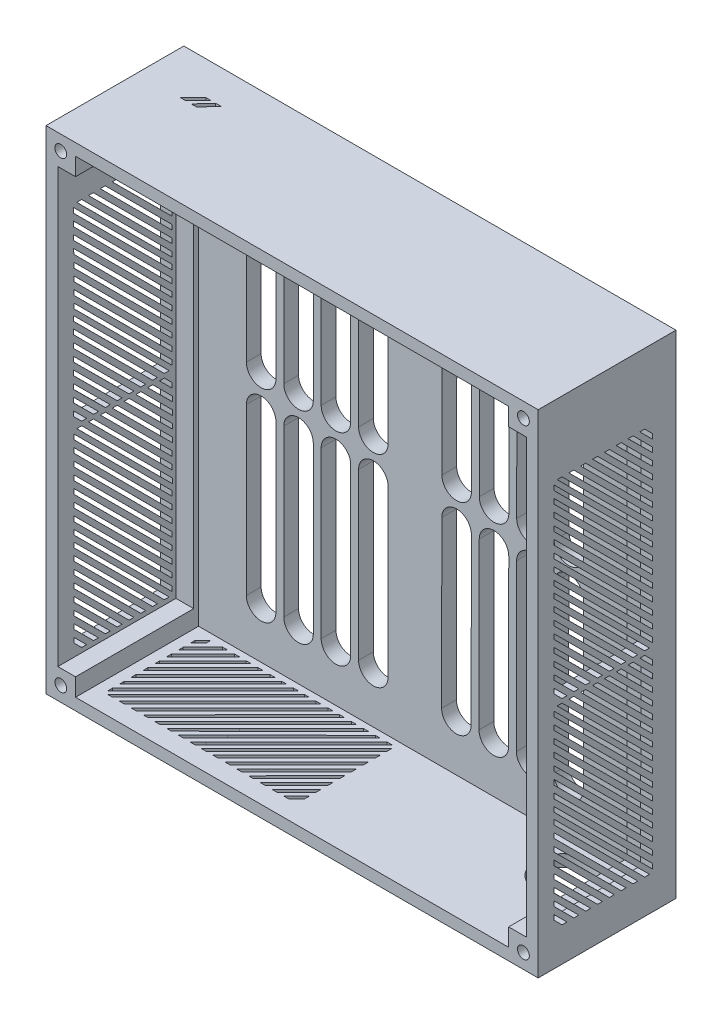
SolidWorks part; units mm, degrees
ref_plane "Plano frontal" through (0, 0, 0) normal (0, 0, 1) x (1, 0, 0)
ref_plane "Plano superior" through (0, 0, 0) normal (0, 1, 0) x (1, 0, 0)
ref_plane "Plano direito" through (0, 0, 0) normal (1, 0, 0) x (0, 0, -1)
sketch "Esboço1" plane through (0, 0, 0) normal (0, 0, 1) x (1, 0, 0)
  line L1 (-16.5696, 239.8339) -> (233.4304, 239.8339)
  line L2 (-16.5696, 239.8339) -> (-16.5696, -10.1661)
  line L3 (-16.5696, -10.1661) -> (233.4304, -10.1661)
  line L4 (233.4304, 239.8339) -> (233.4304, -10.1661)
  dimension "D1" = 250
  dimension "D2" = 250
extrude "Ressalto-extrusão1" add sketch "Esboço1" along normal blind 70 contours L2 L1 L4 L3
sketch "Esboço2" plane through (0, 0, 70) normal (0, 0, 1) x (1, 0, 0)
  line L0 (233.4304, 239.8339) -> (233.4304, -10.1661) construction
  line L1 (-10.5696, 233.8339) -> (227.4304, 233.8339)
  line L2 (-10.5696, 233.8339) -> (-10.5696, -4.1661)
  line L3 (-10.5696, -4.1661) -> (227.4304, -4.1661)
  line L4 (227.4304, 233.8339) -> (227.4304, -4.1661)
  line L5 (-16.5696, 239.8339) -> (233.4304, 239.8339) construction
  line L6 (-16.5696, 239.8339) -> (-16.5696, -10.1661) construction
  line L7 (-16.5696, -10.1661) -> (233.4304, -10.1661) construction
  dimension "D1" = 6
  dimension "D2" = 6
  dimension "D3" = 6
  dimension "D4" = 6
extrude "Corte-extrusão1" cut sketch "Esboço2" against normal blind 60
sketch "Esboço3" plane through (0, 0, 10) normal (0, 0, 1) x (1, 0, 0)
  line L0 (16.5131, 123.2364) -> (114.7807, 123.244)
  line L1 (16.3207, 123.1057) -> (16.3131, 223.614)
  line L2 (16.3748, 223.7141) -> (114.8731, 223.7141)
  line L3 (114.7807, 123.244) -> (114.7731, 223.5216)
  line L4 (215.3156, 223.7537) -> (117.0479, 223.7536)
  line L5 (215.5079, 223.8844) -> (215.5079, 123.3761)
  line L6 (117.0479, 123.4759) -> (215.5079, 123.3761)
  line L7 (117.0479, 223.7536) -> (117.0479, 123.4759)
  line L10 (16.567, 20.9373) -> (114.8346, 20.9449)
  line L11 (16.3746, 20.8067) -> (16.367, 121.3149)
  line L12 (16.4288, 121.4073) -> (99.2081, 121.4137)
  line L13 (114.8346, 20.9449) -> (114.827, 121.2225)
  line L14 (215.3478, 121.4314) -> (117.0801, 121.4238)
  line L15 (215.5401, 121.5621) -> (215.5477, 21.0538)
  line L16 (215.486, 20.9614) -> (116.9877, 20.9538)
  line L17 (117.0801, 121.4238) -> (117.0877, 21.1462)
  line L21 (-16.5696, -10.1661) -> (233.4304, -10.1661) construction
  line L23 (114.7807, 123.244) -> (117.0801, 121.4238) construction
  line L24 (99.2081, 121.4137) -> (114.827, 121.2225)
  line L25 (-16.5696, 239.8339) -> (233.4304, -10.1661) construction
  line L26 (-16.5696, -10.1661) -> (233.4304, 239.8339) construction
  arc A0 (59.4431, 138.154) -> (59.4431, 125.154) centre (59.4431, 131.654) ccw
  arc A1 (59.4431, 125.154) -> (59.4431, 138.154) centre (59.4431, 131.654) ccw
  arc A2 (40.4431, 138.154) -> (40.4431, 125.154) centre (40.4431, 131.654) ccw
  arc A3 (40.4431, 125.154) -> (40.4431, 138.154) centre (40.4431, 131.654) ccw
  arc A4 (40.4431, 152.154) -> (40.4431, 139.154) centre (40.4431, 145.654) ccw
  arc A5 (40.4431, 139.154) -> (40.4431, 152.154) centre (40.4431, 145.654) ccw
  arc A6 (59.4431, 152.154) -> (59.4431, 139.154) centre (59.4431, 145.654) ccw
  arc A7 (59.4431, 139.154) -> (59.4431, 152.154) centre (59.4431, 145.654) ccw
  arc A8 (78.4431, 152.154) -> (78.4431, 139.154) centre (78.4431, 145.654) ccw
  arc A9 (78.4431, 139.154) -> (78.4431, 152.154) centre (78.4431, 145.654) ccw
  arc A10 (78.4431, 138.154) -> (78.4431, 125.154) centre (78.4431, 131.654) ccw
  arc A11 (78.4431, 125.154) -> (78.4431, 138.154) centre (78.4431, 131.654) ccw
  arc A12 (97.4431, 138.154) -> (97.4431, 125.154) centre (97.4431, 131.654) ccw
  arc A13 (97.4431, 125.154) -> (97.4431, 138.154) centre (97.4431, 131.654) ccw
  arc A14 (97.4431, 152.154) -> (97.4431, 139.154) centre (97.4431, 145.654) ccw
  arc A15 (97.4431, 139.154) -> (97.4431, 152.154) centre (97.4431, 145.654) ccw
  arc A16 (97.4431, 166.154) -> (97.4431, 153.154) centre (97.4431, 159.654) ccw
  arc A17 (97.4431, 153.154) -> (97.4431, 166.154) centre (97.4431, 159.654) ccw
  arc A18 (78.4431, 166.154) -> (78.4431, 153.154) centre (78.4431, 159.654) ccw
  arc A19 (78.4431, 153.154) -> (78.4431, 166.154) centre (78.4431, 159.654) ccw
  arc A20 (59.4431, 166.154) -> (59.4431, 153.154) centre (59.4431, 159.654) ccw
  arc A21 (59.4431, 153.154) -> (59.4431, 166.154) centre (59.4431, 159.654) ccw
  arc A22 (40.4431, 166.154) -> (40.4431, 153.154) centre (40.4431, 159.654) ccw
  arc A23 (40.4431, 153.154) -> (40.4431, 166.154) centre (40.4431, 159.654) ccw
  arc A24 (40.4431, 180.154) -> (40.4431, 167.154) centre (40.4431, 173.654) ccw
  arc A25 (40.4431, 167.154) -> (40.4431, 180.154) centre (40.4431, 173.654) ccw
  arc A26 (59.4431, 180.154) -> (59.4431, 167.154) centre (59.4431, 173.654) ccw
  arc A27 (59.4431, 167.154) -> (59.4431, 180.154) centre (59.4431, 173.654) ccw
  arc A28 (78.4431, 180.154) -> (78.4431, 167.154) centre (78.4431, 173.654) ccw
  arc A29 (78.4431, 167.154) -> (78.4431, 180.154) centre (78.4431, 173.654) ccw
  arc A30 (97.4431, 180.154) -> (97.4431, 167.154) centre (97.4431, 173.654) ccw
  arc A31 (97.4431, 167.154) -> (97.4431, 180.154) centre (97.4431, 173.654) ccw
  arc A32 (97.4431, 194.154) -> (97.4431, 181.154) centre (97.4431, 187.654) ccw
  arc A33 (97.4431, 181.154) -> (97.4431, 194.154) centre (97.4431, 187.654) ccw
  arc A34 (78.4431, 194.154) -> (78.4431, 181.154) centre (78.4431, 187.654) ccw
  arc A35 (78.4431, 181.154) -> (78.4431, 194.154) centre (78.4431, 187.654) ccw
  arc A36 (59.4431, 194.154) -> (59.4431, 181.154) centre (59.4431, 187.654) ccw
  arc A37 (59.4431, 181.154) -> (59.4431, 194.154) centre (59.4431, 187.654) ccw
  arc A38 (40.4431, 194.154) -> (40.4431, 181.154) centre (40.4431, 187.654) ccw
  arc A39 (40.4431, 181.154) -> (40.4431, 194.154) centre (40.4431, 187.654) ccw
  arc A40 (40.4431, 208.154) -> (40.4431, 195.154) centre (40.4431, 201.654) ccw
  arc A41 (40.4431, 195.154) -> (40.4431, 208.154) centre (40.4431, 201.654) ccw
  arc A42 (59.4431, 208.154) -> (59.4431, 195.154) centre (59.4431, 201.654) ccw
  arc A43 (59.4431, 195.154) -> (59.4431, 208.154) centre (59.4431, 201.654) ccw
  arc A44 (78.4431, 208.154) -> (78.4431, 195.154) centre (78.4431, 201.654) ccw
  arc A45 (78.4431, 195.154) -> (78.4431, 208.154) centre (78.4431, 201.654) ccw
  arc A46 (97.4431, 208.154) -> (97.4431, 195.154) centre (97.4431, 201.654) ccw
  arc A47 (97.4431, 195.154) -> (97.4431, 208.154) centre (97.4431, 201.654) ccw
  arc A48 (97.4431, 222.154) -> (97.4431, 209.154) centre (97.4431, 215.654) ccw
  arc A49 (97.4431, 209.154) -> (97.4431, 222.154) centre (97.4431, 215.654) ccw
  arc A50 (78.4431, 222.154) -> (78.4431, 209.154) centre (78.4431, 215.654) ccw
  arc A51 (78.4431, 209.154) -> (78.4431, 222.154) centre (78.4431, 215.654) ccw
  arc A52 (59.4431, 222.154) -> (59.4431, 209.154) centre (59.4431, 215.654) ccw
  arc A53 (59.4431, 209.154) -> (59.4431, 222.154) centre (59.4431, 215.654) ccw
  arc A54 (40.4431, 222.154) -> (40.4431, 209.154) centre (40.4431, 215.654) ccw
  arc A55 (40.4431, 209.154) -> (40.4431, 222.154) centre (40.4431, 215.654) ccw
  circle A56 centre (20.8131, 210.774) radius 0.975
  circle A57 centre (20.9431, 217.524) radius 0.975
  circle A58 centre (110.4831, 207.064) radius 0.975
  circle A59 centre (110.4831, 213.114) radius 0.975
  circle A60 centre (110.6631, 136.644) radius 0.975
  circle A61 centre (110.6031, 142.634) radius 0.975
  circle A62 centre (20.6431, 132.314) radius 0.975
  circle A63 centre (20.6431, 138.364) radius 0.975
  arc A64 (172.3779, 208.8361) -> (172.3779, 221.8361) centre (172.3779, 215.3361) ccw
  arc A65 (172.3779, 221.8361) -> (172.3779, 208.8361) centre (172.3779, 215.3361) ccw
  arc A66 (191.3779, 208.8361) -> (191.3779, 221.8361) centre (191.3779, 215.3361) ccw
  arc A67 (191.3779, 221.8361) -> (191.3779, 208.8361) centre (191.3779, 215.3361) ccw
  arc A68 (191.3779, 194.8361) -> (191.3779, 207.8361) centre (191.3779, 201.3361) ccw
  arc A69 (191.3779, 207.8361) -> (191.3779, 194.8361) centre (191.3779, 201.3361) ccw
  arc A70 (172.3779, 194.8361) -> (172.3779, 207.8361) centre (172.3779, 201.3361) ccw
  arc A71 (172.3779, 207.8361) -> (172.3779, 194.8361) centre (172.3779, 201.3361) ccw
  arc A72 (153.3779, 194.8361) -> (153.3779, 207.8361) centre (153.3779, 201.3361) ccw
  arc A73 (153.3779, 207.8361) -> (153.3779, 194.8361) centre (153.3779, 201.3361) ccw
  arc A74 (153.3779, 208.8361) -> (153.3779, 221.8361) centre (153.3779, 215.3361) ccw
  arc A75 (153.3779, 221.8361) -> (153.3779, 208.8361) centre (153.3779, 215.3361) ccw
  arc A76 (134.3779, 208.8361) -> (134.3779, 221.8361) centre (134.3779, 215.3361) ccw
  arc A77 (134.3779, 221.8361) -> (134.3779, 208.8361) centre (134.3779, 215.3361) ccw
  arc A78 (134.3779, 194.8361) -> (134.3779, 207.8361) centre (134.3779, 201.3361) ccw
  arc A79 (134.3779, 207.8361) -> (134.3779, 194.8361) centre (134.3779, 201.3361) ccw
  arc A80 (134.3779, 180.8361) -> (134.3779, 193.8361) centre (134.3779, 187.3361) ccw
  arc A81 (134.3779, 193.8361) -> (134.3779, 180.8361) centre (134.3779, 187.3361) ccw
  arc A82 (153.3779, 180.8361) -> (153.3779, 193.8361) centre (153.3779, 187.3361) ccw
  arc A83 (153.3779, 193.8361) -> (153.3779, 180.8361) centre (153.3779, 187.3361) ccw
  arc A84 (172.3779, 180.8361) -> (172.3779, 193.8361) centre (172.3779, 187.3361) ccw
  arc A85 (172.3779, 193.8361) -> (172.3779, 180.8361) centre (172.3779, 187.3361) ccw
  arc A86 (191.3779, 180.8361) -> (191.3779, 193.8361) centre (191.3779, 187.3361) ccw
  arc A87 (191.3779, 193.8361) -> (191.3779, 180.8361) centre (191.3779, 187.3361) ccw
  arc A88 (191.3779, 166.8361) -> (191.3779, 179.8361) centre (191.3779, 173.3361) ccw
  arc A89 (191.3779, 179.8361) -> (191.3779, 166.8361) centre (191.3779, 173.3361) ccw
  arc A90 (172.3779, 166.8361) -> (172.3779, 179.8361) centre (172.3779, 173.3361) ccw
  arc A91 (172.3779, 179.8361) -> (172.3779, 166.8361) centre (172.3779, 173.3361) ccw
  arc A92 (153.3779, 166.8361) -> (153.3779, 179.8361) centre (153.3779, 173.3361) ccw
  arc A93 (153.3779, 179.8361) -> (153.3779, 166.8361) centre (153.3779, 173.3361) ccw
  arc A94 (134.3779, 166.8361) -> (134.3779, 179.8361) centre (134.3779, 173.3361) ccw
  arc A95 (134.3779, 179.8361) -> (134.3779, 166.8361) centre (134.3779, 173.3361) ccw
  arc A96 (134.3779, 152.8361) -> (134.3779, 165.8361) centre (134.3779, 159.3361) ccw
  arc A97 (134.3779, 165.8361) -> (134.3779, 152.8361) centre (134.3779, 159.3361) ccw
  arc A98 (153.3779, 152.8361) -> (153.3779, 165.8361) centre (153.3779, 159.3361) ccw
  arc A99 (153.3779, 165.8361) -> (153.3779, 152.8361) centre (153.3779, 159.3361) ccw
  arc A100 (172.3779, 152.8361) -> (172.3779, 165.8361) centre (172.3779, 159.3361) ccw
  arc A101 (172.3779, 165.8361) -> (172.3779, 152.8361) centre (172.3779, 159.3361) ccw
  arc A102 (191.3779, 152.8361) -> (191.3779, 165.8361) centre (191.3779, 159.3361) ccw
  arc A103 (191.3779, 165.8361) -> (191.3779, 152.8361) centre (191.3779, 159.3361) ccw
  arc A104 (191.3779, 138.8361) -> (191.3779, 151.8361) centre (191.3779, 145.3361) ccw
  arc A105 (191.3779, 151.8361) -> (191.3779, 138.8361) centre (191.3779, 145.3361) ccw
  arc A106 (172.3779, 138.8361) -> (172.3779, 151.8361) centre (172.3779, 145.3361) ccw
  arc A107 (172.3779, 151.8361) -> (172.3779, 138.8361) centre (172.3779, 145.3361) ccw
  arc A108 (153.3779, 138.8361) -> (153.3779, 151.8361) centre (153.3779, 145.3361) ccw
  arc A109 (153.3779, 151.8361) -> (153.3779, 138.8361) centre (153.3779, 145.3361) ccw
  arc A110 (134.3779, 138.8361) -> (134.3779, 151.8361) centre (134.3779, 145.3361) ccw
  arc A111 (134.3779, 151.8361) -> (134.3779, 138.8361) centre (134.3779, 145.3361) ccw
  arc A112 (134.3779, 124.8361) -> (134.3779, 137.8361) centre (134.3779, 131.3361) ccw
  arc A113 (134.3779, 137.8361) -> (134.3779, 124.8361) centre (134.3779, 131.3361) ccw
  arc A114 (153.3779, 124.8361) -> (153.3779, 137.8361) centre (153.3779, 131.3361) ccw
  arc A115 (153.3779, 137.8361) -> (153.3779, 124.8361) centre (153.3779, 131.3361) ccw
  arc A116 (172.3779, 124.8361) -> (172.3779, 137.8361) centre (172.3779, 131.3361) ccw
  arc A117 (172.3779, 137.8361) -> (172.3779, 124.8361) centre (172.3779, 131.3361) ccw
  arc A118 (191.3779, 124.8361) -> (191.3779, 137.8361) centre (191.3779, 131.3361) ccw
  arc A119 (191.3779, 137.8361) -> (191.3779, 124.8361) centre (191.3779, 131.3361) ccw
  circle A120 centre (211.0079, 136.2161) radius 0.975
  circle A121 centre (210.8779, 129.4661) radius 0.975
  circle A122 centre (121.3379, 139.9261) radius 0.975
  circle A123 centre (121.3379, 133.8761) radius 0.975
  circle A124 centre (121.1579, 210.3461) radius 0.975
  circle A125 centre (121.2179, 204.3561) radius 0.975
  circle A126 centre (211.1779, 214.6761) radius 0.975
  circle A127 centre (211.1779, 208.6261) radius 0.975
  arc A128 (59.497, 35.8549) -> (59.497, 22.8549) centre (59.497, 29.3549) ccw
  arc A129 (59.497, 22.8549) -> (59.497, 35.8549) centre (59.497, 29.3549) ccw
  arc A130 (40.497, 35.8549) -> (40.497, 22.8549) centre (40.497, 29.3549) ccw
  arc A131 (40.497, 22.8549) -> (40.497, 35.8549) centre (40.497, 29.3549) ccw
  arc A132 (40.497, 49.8549) -> (40.497, 36.8549) centre (40.497, 43.3549) ccw
  arc A133 (40.497, 36.8549) -> (40.497, 49.8549) centre (40.497, 43.3549) ccw
  arc A134 (59.497, 49.8549) -> (59.497, 36.8549) centre (59.497, 43.3549) ccw
  arc A135 (59.497, 36.8549) -> (59.497, 49.8549) centre (59.497, 43.3549) ccw
  arc A136 (78.497, 49.8549) -> (78.497, 36.8549) centre (78.497, 43.3549) ccw
  arc A137 (78.497, 36.8549) -> (78.497, 49.8549) centre (78.497, 43.3549) ccw
  arc A138 (78.497, 35.8549) -> (78.497, 22.8549) centre (78.497, 29.3549) ccw
  arc A139 (78.497, 22.8549) -> (78.497, 35.8549) centre (78.497, 29.3549) ccw
  arc A140 (97.497, 35.8549) -> (97.497, 22.8549) centre (97.497, 29.3549) ccw
  arc A141 (97.497, 22.8549) -> (97.497, 35.8549) centre (97.497, 29.3549) ccw
  arc A142 (97.497, 49.8549) -> (97.497, 36.8549) centre (97.497, 43.3549) ccw
  arc A143 (97.497, 36.8549) -> (97.497, 49.8549) centre (97.497, 43.3549) ccw
  arc A144 (97.497, 63.8549) -> (97.497, 50.8549) centre (97.497, 57.3549) ccw
  arc A145 (97.497, 50.8549) -> (97.497, 63.8549) centre (97.497, 57.3549) ccw
  arc A146 (78.497, 63.8549) -> (78.497, 50.8549) centre (78.497, 57.3549) ccw
  arc A147 (78.497, 50.8549) -> (78.497, 63.8549) centre (78.497, 57.3549) ccw
  arc A148 (59.497, 63.8549) -> (59.497, 50.8549) centre (59.497, 57.3549) ccw
  arc A149 (59.497, 50.8549) -> (59.497, 63.8549) centre (59.497, 57.3549) ccw
  arc A150 (40.497, 63.8549) -> (40.497, 50.8549) centre (40.497, 57.3549) ccw
  arc A151 (40.497, 50.8549) -> (40.497, 63.8549) centre (40.497, 57.3549) ccw
  arc A152 (40.497, 77.8549) -> (40.497, 64.8549) centre (40.497, 71.3549) ccw
  arc A153 (40.497, 64.8549) -> (40.497, 77.8549) centre (40.497, 71.3549) ccw
  arc A154 (59.497, 77.8549) -> (59.497, 64.8549) centre (59.497, 71.3549) ccw
  arc A155 (59.497, 64.8549) -> (59.497, 77.8549) centre (59.497, 71.3549) ccw
  arc A156 (78.497, 77.8549) -> (78.497, 64.8549) centre (78.497, 71.3549) ccw
  arc A157 (78.497, 64.8549) -> (78.497, 77.8549) centre (78.497, 71.3549) ccw
  arc A158 (97.497, 77.8549) -> (97.497, 64.8549) centre (97.497, 71.3549) ccw
  arc A159 (97.497, 64.8549) -> (97.497, 77.8549) centre (97.497, 71.3549) ccw
  arc A160 (97.497, 91.8549) -> (97.497, 78.8549) centre (97.497, 85.3549) ccw
  arc A161 (97.497, 78.8549) -> (97.497, 91.8549) centre (97.497, 85.3549) ccw
  arc A162 (78.497, 91.8549) -> (78.497, 78.8549) centre (78.497, 85.3549) ccw
  arc A163 (78.497, 78.8549) -> (78.497, 91.8549) centre (78.497, 85.3549) ccw
  arc A164 (59.497, 91.8549) -> (59.497, 78.8549) centre (59.497, 85.3549) ccw
  arc A165 (59.497, 78.8549) -> (59.497, 91.8549) centre (59.497, 85.3549) ccw
  arc A166 (40.497, 91.8549) -> (40.497, 78.8549) centre (40.497, 85.3549) ccw
  arc A167 (40.497, 78.8549) -> (40.497, 91.8549) centre (40.497, 85.3549) ccw
  arc A168 (40.497, 105.8549) -> (40.497, 92.8549) centre (40.497, 99.3549) ccw
  arc A169 (40.497, 92.8549) -> (40.497, 105.8549) centre (40.497, 99.3549) ccw
  arc A170 (59.497, 105.8549) -> (59.497, 92.8549) centre (59.497, 99.3549) ccw
  arc A171 (59.497, 92.8549) -> (59.497, 105.8549) centre (59.497, 99.3549) ccw
  arc A172 (78.497, 105.8549) -> (78.497, 92.8549) centre (78.497, 99.3549) ccw
  arc A173 (78.497, 92.8549) -> (78.497, 105.8549) centre (78.497, 99.3549) ccw
  arc A174 (97.497, 105.8549) -> (97.497, 92.8549) centre (97.497, 99.3549) ccw
  arc A175 (97.497, 92.8549) -> (97.497, 105.8549) centre (97.497, 99.3549) ccw
  arc A176 (97.497, 119.8549) -> (97.497, 106.8549) centre (97.497, 113.3549) ccw
  arc A177 (97.497, 106.8549) -> (97.497, 119.8549) centre (97.497, 113.3549) ccw
  arc A178 (78.497, 119.8549) -> (78.497, 106.8549) centre (78.497, 113.3549) ccw
  arc A179 (78.497, 106.8549) -> (78.497, 119.8549) centre (78.497, 113.3549) ccw
  arc A180 (59.497, 119.8549) -> (59.497, 106.8549) centre (59.497, 113.3549) ccw
  arc A181 (59.497, 106.8549) -> (59.497, 119.8549) centre (59.497, 113.3549) ccw
  arc A182 (40.497, 119.8549) -> (40.497, 106.8549) centre (40.497, 113.3549) ccw
  arc A183 (40.497, 106.8549) -> (40.497, 119.8549) centre (40.497, 113.3549) ccw
  circle A184 centre (20.867, 108.4749) radius 0.975
  circle A185 centre (20.997, 115.2249) radius 0.975
  circle A186 centre (110.537, 104.7649) radius 0.975
  circle A187 centre (110.537, 110.8149) radius 0.975
  circle A188 centre (110.717, 34.3449) radius 0.975
  circle A189 centre (110.657, 40.3349) radius 0.975
  circle A190 centre (20.697, 30.0149) radius 0.975
  circle A191 centre (20.697, 36.0649) radius 0.975
  arc A192 (172.4177, 106.5138) -> (172.4177, 119.5138) centre (172.4177, 113.0138) ccw
  arc A193 (172.4177, 119.5138) -> (172.4177, 106.5138) centre (172.4177, 113.0138) ccw
  arc A194 (191.4177, 106.5138) -> (191.4177, 119.5138) centre (191.4177, 113.0138) ccw
  arc A195 (191.4177, 119.5138) -> (191.4177, 106.5138) centre (191.4177, 113.0138) ccw
  arc A196 (191.4177, 92.5138) -> (191.4177, 105.5138) centre (191.4177, 99.0138) ccw
  arc A197 (191.4177, 105.5138) -> (191.4177, 92.5138) centre (191.4177, 99.0138) ccw
  arc A198 (172.4177, 92.5138) -> (172.4177, 105.5138) centre (172.4177, 99.0138) ccw
  arc A199 (172.4177, 105.5138) -> (172.4177, 92.5138) centre (172.4177, 99.0138) ccw
  arc A200 (153.4177, 92.5138) -> (153.4177, 105.5138) centre (153.4177, 99.0138) ccw
  arc A201 (153.4177, 105.5138) -> (153.4177, 92.5138) centre (153.4177, 99.0138) ccw
  arc A202 (153.4177, 106.5138) -> (153.4177, 119.5138) centre (153.4177, 113.0138) ccw
  arc A203 (153.4177, 119.5138) -> (153.4177, 106.5138) centre (153.4177, 113.0138) ccw
  arc A204 (134.4177, 106.5138) -> (134.4177, 119.5138) centre (134.4177, 113.0138) ccw
  arc A205 (134.4177, 119.5138) -> (134.4177, 106.5138) centre (134.4177, 113.0138) ccw
  arc A206 (134.4177, 92.5138) -> (134.4177, 105.5138) centre (134.4177, 99.0138) ccw
  arc A207 (134.4177, 105.5138) -> (134.4177, 92.5138) centre (134.4177, 99.0138) ccw
  arc A208 (134.4177, 78.5138) -> (134.4177, 91.5138) centre (134.4177, 85.0138) ccw
  arc A209 (134.4177, 91.5138) -> (134.4177, 78.5138) centre (134.4177, 85.0138) ccw
  arc A210 (153.4177, 78.5138) -> (153.4177, 91.5138) centre (153.4177, 85.0138) ccw
  arc A211 (153.4177, 91.5138) -> (153.4177, 78.5138) centre (153.4177, 85.0138) ccw
  arc A212 (172.4177, 78.5138) -> (172.4177, 91.5138) centre (172.4177, 85.0138) ccw
  arc A213 (172.4177, 91.5138) -> (172.4177, 78.5138) centre (172.4177, 85.0138) ccw
  arc A214 (191.4177, 78.5138) -> (191.4177, 91.5138) centre (191.4177, 85.0138) ccw
  arc A215 (191.4177, 91.5138) -> (191.4177, 78.5138) centre (191.4177, 85.0138) ccw
  arc A216 (191.4177, 64.5138) -> (191.4177, 77.5138) centre (191.4177, 71.0138) ccw
  arc A217 (191.4177, 77.5138) -> (191.4177, 64.5138) centre (191.4177, 71.0138) ccw
  arc A218 (172.4177, 64.5138) -> (172.4177, 77.5138) centre (172.4177, 71.0138) ccw
  arc A219 (172.4177, 77.5138) -> (172.4177, 64.5138) centre (172.4177, 71.0138) ccw
  arc A220 (153.4177, 64.5138) -> (153.4177, 77.5138) centre (153.4177, 71.0138) ccw
  arc A221 (153.4177, 77.5138) -> (153.4177, 64.5138) centre (153.4177, 71.0138) ccw
  arc A222 (134.4177, 64.5138) -> (134.4177, 77.5138) centre (134.4177, 71.0138) ccw
  arc A223 (134.4177, 77.5138) -> (134.4177, 64.5138) centre (134.4177, 71.0138) ccw
  arc A224 (134.4177, 50.5138) -> (134.4177, 63.5138) centre (134.4177, 57.0138) ccw
  arc A225 (134.4177, 63.5138) -> (134.4177, 50.5138) centre (134.4177, 57.0138) ccw
  arc A226 (153.4177, 50.5138) -> (153.4177, 63.5138) centre (153.4177, 57.0138) ccw
  arc A227 (153.4177, 63.5138) -> (153.4177, 50.5138) centre (153.4177, 57.0138) ccw
  arc A228 (172.4177, 50.5138) -> (172.4177, 63.5138) centre (172.4177, 57.0138) ccw
  arc A229 (172.4177, 63.5138) -> (172.4177, 50.5138) centre (172.4177, 57.0138) ccw
  arc A230 (191.4177, 50.5138) -> (191.4177, 63.5138) centre (191.4177, 57.0138) ccw
  arc A231 (191.4177, 63.5138) -> (191.4177, 50.5138) centre (191.4177, 57.0138) ccw
  arc A232 (191.4177, 36.5138) -> (191.4177, 49.5138) centre (191.4177, 43.0138) ccw
  arc A233 (191.4177, 49.5138) -> (191.4177, 36.5138) centre (191.4177, 43.0138) ccw
  arc A234 (172.4177, 36.5138) -> (172.4177, 49.5138) centre (172.4177, 43.0138) ccw
  arc A235 (172.4177, 49.5138) -> (172.4177, 36.5138) centre (172.4177, 43.0138) ccw
  arc A236 (153.4177, 36.5138) -> (153.4177, 49.5138) centre (153.4177, 43.0138) ccw
  arc A237 (153.4177, 49.5138) -> (153.4177, 36.5138) centre (153.4177, 43.0138) ccw
  arc A238 (134.4177, 36.5138) -> (134.4177, 49.5138) centre (134.4177, 43.0138) ccw
  arc A239 (134.4177, 49.5138) -> (134.4177, 36.5138) centre (134.4177, 43.0138) ccw
  arc A240 (134.4177, 22.5138) -> (134.4177, 35.5138) centre (134.4177, 29.0138) ccw
  arc A241 (134.4177, 35.5138) -> (134.4177, 22.5138) centre (134.4177, 29.0138) ccw
  arc A242 (153.4177, 22.5138) -> (153.4177, 35.5138) centre (153.4177, 29.0138) ccw
  arc A243 (153.4177, 35.5138) -> (153.4177, 22.5138) centre (153.4177, 29.0138) ccw
  arc A244 (172.4177, 22.5138) -> (172.4177, 35.5138) centre (172.4177, 29.0138) ccw
  arc A245 (172.4177, 35.5138) -> (172.4177, 22.5138) centre (172.4177, 29.0138) ccw
  arc A246 (191.4177, 22.5138) -> (191.4177, 35.5138) centre (191.4177, 29.0138) ccw
  arc A247 (191.4177, 35.5138) -> (191.4177, 22.5138) centre (191.4177, 29.0138) ccw
  circle A248 centre (211.0477, 33.8938) radius 0.975
  circle A249 centre (210.9177, 27.1438) radius 0.975
  circle A250 centre (121.3777, 37.6038) radius 0.975
  circle A251 centre (121.3777, 31.5538) radius 0.975
  circle A252 centre (121.1977, 108.0238) radius 0.975
  circle A253 centre (121.2577, 102.0338) radius 0.975
  circle A254 centre (211.2177, 112.3538) radius 0.975
  circle A255 centre (211.2177, 106.3038) radius 0.975
  point P135 (166.2214, 173.6225)
  point P406 (166.2574, 71.2965)
  point P544 (115.9304, 122.3339)
  point P546 (115.9304, 122.3339)
sketch "Esboço5" plane through (0, 239.8339, 0) normal (0, 1, 0) x (1, 0, 0)
  line L0 (39.532, 0) -> (39.532, -40.1721)
  line L1 (-16.5696, 0) -> (233.4304, 0) construction
  line L2 (-48.9022, 48.2621) -> (39.532, -40.1721)
  line L3 (127.9662, 48.2621) -> (39.532, -40.1721)
  line L4 (-48.9022, 48.2621) -> (-150.6401, 150) construction
  line L5 (39.532, 0) -> (39.532, 150) construction
  line L6 (-150.6401, 150) -> (229.7041, 150) construction
  line L7 (127.9662, 48.2621) -> (375.3202, 295.6161) construction
  arc A0 (-48.9022, 48.2621) -> (127.9662, 48.2621) centre (39.532, -40.1721) cw
  dimension "D1" = 90
  dimension "D2" = 45
sketch "Esboço6" plane through (0, 0, 10) normal (0, 0, 1) x (1, 0, 0)
  line L0 (22.6955, 208.1676) -> (22.6955, 124.154)
  line L1 (37.6955, 208.1676) -> (37.6955, 124.154)
  line L2 (41.6955, 208.1676) -> (41.6955, 124.154)
  line L3 (56.6955, 124.154) -> (56.6955, 208.1676)
  line L4 (60.6955, 208.1676) -> (60.6955, 124.154)
  line L5 (79.6955, 208.1676) -> (79.6955, 124.154)
  line L6 (75.6955, 124.154) -> (75.6955, 208.1676)
  line L7 (94.6955, 124.154) -> (94.6955, 208.1676)
  line L9 (94.6955, 105.5138) -> (94.6955, 21.5002)
  line L17 (-10.5696, 114.8339) -> (227.4304, 114.8339) construction
  line L18 (-10.5696, 233.8339) -> (-10.5696, -4.1661) construction
  line L19 (227.4304, -4.1661) -> (227.4304, 233.8339) construction
  line L20 (75.6955, 105.5138) -> (75.6955, 21.5002)
  line L21 (79.6955, 21.5002) -> (79.6955, 105.5138)
  line L22 (60.6955, 21.5002) -> (60.6955, 105.5138)
  line L23 (56.6955, 105.5138) -> (56.6955, 21.5002)
  line L24 (41.6955, 21.5002) -> (41.6955, 105.5138)
  line L25 (37.6955, 21.5002) -> (37.6955, 105.5138)
  line L26 (22.6955, 21.5002) -> (22.6955, 105.5138)
  line L27 (193.8751, 21.3832) -> (193.9899, 105.3967)
  line L28 (108.418, 215.6572) -> (108.4304, 233.8339) construction
  line L29 (227.4304, 233.8339) -> (-10.5696, 233.8339) construction
  line L30 (178.8751, 21.4037) -> (178.9899, 105.4172)
  line L31 (174.8751, 21.4092) -> (174.9899, 105.4227)
  line L32 (159.9899, 105.4432) -> (159.8751, 21.4297)
  line L33 (155.8751, 21.4351) -> (155.9899, 105.4487)
  line L34 (136.8752, 21.4611) -> (136.99, 105.4746)
  line L35 (140.99, 105.4692) -> (140.8752, 21.4556)
  line L36 (121.99, 105.4951) -> (121.8752, 21.4816)
  line L37 (122.0155, 124.1353) -> (122.1303, 208.1489)
  line L38 (141.0154, 124.1094) -> (141.1302, 208.1229)
  line L39 (137.1302, 208.1284) -> (137.0154, 124.1148)
  line L40 (156.1302, 208.1024) -> (156.0154, 124.0889)
  line L41 (160.0154, 124.0834) -> (160.1302, 208.0969)
  line L42 (175.1302, 208.0764) -> (175.0154, 124.0629)
  line L43 (179.1302, 208.071) -> (179.0154, 124.0574)
  line L44 (194.1302, 208.0505) -> (194.0154, 124.0369)
  line L45 (-10.5696, -4.1661) -> (227.4304, -4.1661) construction
  arc A112 (37.6955, 208.1676) -> (22.6955, 208.1676) centre (30.1955, 208.1676) ccw
  arc A113 (22.6955, 124.154) -> (37.6955, 124.154) centre (30.1955, 124.154) ccw
  arc A114 (41.6955, 208.1676) -> (56.6955, 208.1676) centre (49.1955, 208.1676) cw
  arc A115 (41.6955, 124.154) -> (56.6955, 124.154) centre (49.1955, 124.154) ccw
  arc A116 (60.6955, 208.1676) -> (75.6955, 208.1676) centre (68.1955, 208.1676) cw
  arc A117 (60.6955, 124.154) -> (75.6955, 124.154) centre (68.1955, 124.154) ccw
  arc A118 (79.6955, 208.1676) -> (94.6955, 208.1676) centre (87.1955, 208.1676) cw
  arc A119 (79.6955, 124.154) -> (94.6955, 124.154) centre (87.1955, 124.154) ccw
  arc A128 (79.6955, 105.5138) -> (94.6955, 105.5138) centre (87.1955, 105.5138) cw
  arc A129 (79.6955, 21.5002) -> (94.6955, 21.5002) centre (87.1955, 21.5002) ccw
  arc A130 (60.6955, 105.5138) -> (75.6955, 105.5138) centre (68.1955, 105.5138) cw
  arc A131 (60.6955, 21.5002) -> (75.6955, 21.5002) centre (68.1955, 21.5002) ccw
  arc A132 (41.6955, 105.5138) -> (56.6955, 105.5138) centre (49.1955, 105.5138) cw
  arc A133 (41.6955, 21.5002) -> (56.6955, 21.5002) centre (49.1955, 21.5002) ccw
  arc A134 (22.6955, 105.5138) -> (37.6955, 105.5138) centre (30.1955, 105.5138) cw
  arc A135 (37.6955, 21.5002) -> (22.6955, 21.5002) centre (30.1955, 21.5002) cw
  arc A136 (178.8751, 21.4037) -> (193.8751, 21.3832) centre (186.3751, 21.3935) ccw
  arc A137 (193.9899, 105.3967) -> (178.9899, 105.4172) centre (186.4899, 105.407) ccw
  arc A138 (174.8751, 21.4092) -> (159.8751, 21.4297) centre (167.3751, 21.4194) cw
  arc A139 (174.9899, 105.4227) -> (159.9899, 105.4432) centre (167.4899, 105.433) ccw
  arc A140 (155.8751, 21.4351) -> (140.8752, 21.4556) centre (148.3751, 21.4454) cw
  arc A141 (155.9899, 105.4487) -> (140.99, 105.4692) centre (148.49, 105.4589) ccw
  arc A142 (136.8752, 21.4611) -> (121.8752, 21.4816) centre (129.3752, 21.4713) cw
  arc A143 (136.99, 105.4746) -> (121.99, 105.4951) centre (129.49, 105.4849) ccw
  arc A144 (137.0154, 124.1148) -> (122.0155, 124.1353) centre (129.5154, 124.1251) cw
  arc A145 (137.1302, 208.1284) -> (122.1303, 208.1489) centre (129.6303, 208.1386) ccw
  arc A146 (156.0154, 124.0889) -> (141.0154, 124.1094) centre (148.5154, 124.0991) cw
  arc A147 (156.1302, 208.1024) -> (141.1302, 208.1229) centre (148.6302, 208.1127) ccw
  arc A148 (175.0154, 124.0629) -> (160.0154, 124.0834) centre (167.5154, 124.0731) cw
  arc A149 (175.1302, 208.0764) -> (160.1302, 208.0969) centre (167.6302, 208.0867) ccw
  arc A150 (194.0154, 124.0369) -> (179.0154, 124.0574) centre (186.5154, 124.0472) cw
  arc A151 (179.1302, 208.071) -> (194.1302, 208.0505) centre (186.6302, 208.0607) cw
  dimension "D1" = 19
  dimension "D2" = 19
  dimension "D3" = 19
  dimension "D4" = 19
  dimension "D14" = 7.5
  dimension "D15" = 7.5
  dimension "D16" = 7.5
  dimension "D17" = 7.5
  dimension "D5" = 19
  dimension "D6" = 19
  dimension "D7" = 19
  dimension "D8" = 19
  dimension "D9" = 18.9745
  dimension "D10" = 19
  dimension "D11" = 19
  dimension "D12" = 19
  dimension "D13" = 21.2174
extrude "Corte-extrusão2" cut sketch "Esboço6" against normal through all
sketch "Esboço7" plane through (0, 0, 10) normal (0, 0, 1) x (1, 0, 0)
  line L0 (-16.5696, 239.8339) -> (233.4304, -10.1661) construction
  line L1 (-1.5696, 224.8339) -> (218.4304, 224.8339)
  line L2 (-1.5696, 224.8339) -> (-1.5696, -4.1661)
  line L3 (-1.5696, -4.1661) -> (218.4304, -4.1661)
  line L4 (218.4304, 224.8339) -> (218.4304, -4.1661)
  line L5 (-16.5696, 239.8339) -> (-16.5696, -10.1661) construction
  line L8 (233.4304, 239.8339) -> (233.4304, -10.1661) construction
  line L9 (-10.5696, -4.1661) -> (227.4304, -4.1661) construction
  dimension "D1" = 15
  dimension "D2" = 0
  dimension "D3" = 15
extrude "Corte-extrusão3" cut sketch "Esboço7" against normal blind 2.5
sketch "Esboço8" plane through (-16.5696, 0, 0) normal (-1, 0, 0) x (0, 0, 1)
  line L0 (11.921, 154.2979) -> (61.921, 154.2979) construction
  line L7 (11.8956, 54.7334) -> (61.8956, 54.7334) construction
  line L8 (61.921, 106.7358) -> (61.921, 204.2569) construction
  line L9 (61.921, 204.2569) -> (11.921, 204.2569) construction
  line L10 (11.921, 204.2569) -> (11.921, 106.7358) construction
  line L11 (61.8956, 7.1713) -> (61.8956, 104.6924) construction
  line L12 (61.8956, 104.6924) -> (11.8956, 104.6924) construction
  line L13 (11.8956, 104.6924) -> (11.8956, 7.1713) construction
  line L14 (11.921, 200.2952) -> (15.8826, 204.2569)
  line L15 (11.921, 197.7952) -> (18.3826, 204.2569)
  line L16 (18.3826, 204.2569) -> (15.8826, 204.2569)
  line L17 (11.921, 197.7952) -> (11.921, 200.2952)
  line L18 (11.8777, 194.3401) -> (21.783, 204.2569)
  line L19 (11.8791, 191.8401) -> (24.3826, 204.2569)
  line L20 (24.3826, 204.2569) -> (21.783, 204.2569)
  line L21 (11.8791, 191.8401) -> (11.8777, 194.3401)
  line L22 (11.8873, 188.3253) -> (27.8159, 204.2569)
  line L23 (11.8875, 185.8253) -> (30.3826, 204.2569)
  line L24 (30.3826, 204.2569) -> (27.8159, 204.2569)
  line L25 (11.8875, 185.8253) -> (11.8873, 188.3253)
  line L26 (11.8894, 182.3294) -> (33.8197, 204.2569)
  line L27 (11.8893, 179.8294) -> (36.3826, 204.2569)
  line L28 (36.3826, 204.2569) -> (33.8197, 204.2569)
  line L29 (11.8893, 179.8294) -> (11.8894, 182.3294)
  line L30 (11.8909, 176.3272) -> (39.8374, 204.2569)
  line L31 (11.8902, 173.8272) -> (42.3826, 204.2569)
  line L32 (42.3826, 204.2569) -> (39.8374, 204.2569)
  line L33 (11.8902, 173.8272) -> (11.8909, 176.3272)
  line L34 (11.964, 170.2954) -> (45.8826, 204.2569)
  line L35 (11.964, 167.7954) -> (48.4255, 204.2569)
  line L36 (48.4255, 204.2569) -> (45.8826, 204.2569)
  line L37 (11.964, 167.7954) -> (11.964, 170.2954)
  line L38 (11.9213, 164.2955) -> (51.9292, 204.2569)
  line L39 (11.9213, 161.7955) -> (54.4325, 204.2569)
  line L40 (54.4325, 204.2569) -> (51.9292, 204.2569)
  line L41 (11.9213, 161.7955) -> (11.9213, 164.2955)
  line L42 (11.8969, 158.3271) -> (57.8826, 204.2569)
  line L43 (11.8954, 155.8271) -> (60.3826, 204.2569)
  line L44 (60.3826, 204.2569) -> (57.8826, 204.2569)
  line L45 (11.8954, 155.8271) -> (11.8969, 158.3271)
  line L52 (61.4616, 203.7799) -> (11.921, 154.2979) construction
  line L54 (61.9373, 202.7003) -> (61.9343, 200.2003)
  line L55 (13.4501, 154.2705) -> (61.9373, 202.7003)
  line L56 (15.9501, 154.2678) -> (61.9343, 200.2003)
  line L58 (61.9303, 196.7502) -> (61.9273, 194.247)
  line L62 (61.9231, 190.7432) -> (61.9201, 188.2003)
  line L66 (61.916, 184.7003) -> (61.913, 182.1551)
  line L70 (61.9089, 178.7003) -> (61.9058, 176.1374)
  line L74 (61.9018, 172.7003) -> (61.8987, 170.1337)
  line L78 (61.8947, 166.7003) -> (61.8916, 164.1008)
  line L82 (61.8875, 160.7003) -> (61.8846, 158.2003)
  line L85 (60.3662, 156.6835) -> (61.8846, 158.2003)
  line L86 (57.8586, 156.6863) -> (61.8875, 160.7003)
  line L87 (59.4878, 154.2979) -> (11.921, 154.2979) construction
  line L88 (51.9515, 156.6926) -> (61.8947, 166.7003)
  line L93 (11.9641, 146.6845) -> (21.9846, 156.725)
  line L94 (11.9614, 144.1845) -> (24.4772, 156.7223)
  line L96 (11.9614, 144.1845) -> (11.9641, 146.6845)
  line L97 (11.9576, 140.6826) -> (27.8776, 156.7186)
  line L98 (11.9549, 138.1826) -> (30.4163, 156.7159)
  line L100 (11.9549, 138.1826) -> (11.9576, 140.6826)
  line L101 (11.9511, 134.6809) -> (33.919, 156.7121)
  line L102 (11.9484, 132.2108) -> (36.4569, 156.7093)
  line L104 (11.9484, 132.2108) -> (11.9511, 134.6809)
  line L105 (11.9446, 128.6797) -> (39.9246, 156.7056)
  line L106 (11.942, 126.2161) -> (42.4547, 156.7029)
  line L108 (11.942, 126.2161) -> (11.9446, 128.6797)
  line L109 (11.9382, 122.6842) -> (45.924, 156.6991)
  line L110 (11.9355, 120.2261) -> (48.4465, 156.6964)
  line L112 (11.9355, 120.2261) -> (11.9382, 122.6842)
  line L113 (11.9317, 116.6928) -> (51.9515, 156.6926)
  line L114 (11.929, 114.2364) -> (54.4661, 156.6899)
  line L116 (11.929, 114.2364) -> (11.9317, 116.6928)
  line L117 (11.9223, 110.7277) -> (57.8586, 156.6863)
  line L118 (11.9226, 108.2923) -> (60.3662, 156.6835)
  line L120 (11.9226, 108.2923) -> (11.9223, 110.7277)
  line L121 (59.0601, 153.8241) -> (11.921, 106.7358) construction
  line L122 (13.4774, 106.7358) -> (15.9128, 106.7328)
  line L123 (61.921, 155.1271) -> (61.921, 152.6195)
  line L124 (13.4774, 106.7358) -> (61.921, 155.1271)
  line L125 (15.9128, 106.7328) -> (61.921, 152.6195)
  line L126 (19.4216, 106.7358) -> (21.8779, 106.7358)
  line L127 (61.921, 149.227) -> (61.921, 146.7124)
  line L128 (19.4216, 106.7358) -> (61.921, 149.227)
  line L129 (21.8779, 106.7358) -> (61.921, 146.7124)
  line L130 (25.4113, 106.7358) -> (27.8694, 106.7358)
  line L131 (61.921, 143.2074) -> (61.921, 140.6849)
  line L132 (25.4113, 106.7358) -> (61.921, 143.2074)
  line L133 (27.8694, 106.7358) -> (61.921, 140.6849)
  line L134 (31.4013, 106.7358) -> (33.8649, 106.7358)
  line L135 (61.921, 137.2156) -> (61.921, 134.6855)
  line L136 (31.4013, 106.7358) -> (61.921, 137.2156)
  line L137 (33.8649, 106.7358) -> (61.921, 134.6855)
  line L138 (37.3959, 106.7358) -> (39.8661, 106.7358)
  line L139 (61.921, 131.2178) -> (61.921, 128.6799)
  line L140 (37.3959, 106.7358) -> (61.921, 131.2178)
  line L141 (39.8661, 106.7358) -> (61.921, 128.6799)
  line L142 (43.3678, 106.7358) -> (45.8678, 106.7358)
  line L143 (61.921, 125.1772) -> (61.921, 122.6385)
  line L144 (43.3678, 106.7358) -> (61.921, 125.1772)
  line L145 (45.8678, 106.7358) -> (61.921, 122.6385)
  line L146 (49.3696, 106.7358) -> (51.8696, 106.7358)
  line L147 (61.921, 119.2381) -> (61.921, 116.7455)
  line L148 (49.3696, 106.7358) -> (61.921, 119.2381)
  line L149 (51.8696, 106.7358) -> (61.921, 116.7455)
  line L150 (55.4125, 106.7358) -> (57.9125, 106.7358)
  line L151 (61.9313, 113.2276) -> (61.921, 110.7276)
  line L152 (55.4125, 106.7358) -> (61.9313, 113.2276)
  line L153 (57.9125, 106.7358) -> (61.921, 110.7276)
  line L154 (13.4501, 154.2705) -> (11.921, 152.7432)
  line L155 (11.921, 152.7432) -> (11.921, 150.2432)
  line L156 (11.921, 150.2432) -> (15.9501, 154.2678)
  line L157 (21.9846, 156.725) -> (61.9303, 196.7502)
  line L158 (24.4772, 156.7223) -> (61.9273, 194.247)
  line L159 (27.8776, 156.7186) -> (61.9231, 190.7432)
  line L160 (30.4163, 156.7159) -> (61.9201, 188.2003)
  line L161 (13.4774, 106.7358) -> (61.921, 106.7358) construction
  line L162 (54.4661, 156.6899) -> (61.8916, 164.1008)
  line L163 (45.924, 156.6991) -> (61.9018, 172.7003)
  line L164 (48.4465, 156.6964) -> (61.8987, 170.1337)
  line L165 (39.9246, 156.7056) -> (61.9089, 178.7003)
  line L166 (42.4547, 156.7029) -> (61.9058, 176.1374)
  line L167 (33.919, 156.7121) -> (61.916, 184.7003)
  line L168 (36.4569, 156.7093) -> (61.913, 182.1551)
  line L169 (11.8956, 100.7307) -> (15.8573, 104.6924)
  line L170 (11.8956, 98.2307) -> (18.3573, 104.6924)
  line L171 (18.3573, 104.6924) -> (15.8573, 104.6924)
  line L172 (11.8956, 98.2307) -> (11.8956, 100.7307)
  line L173 (11.8523, 94.7756) -> (21.7577, 104.6924)
  line L174 (11.8538, 92.2756) -> (24.3573, 104.6924)
  line L175 (24.3573, 104.6924) -> (21.7577, 104.6924)
  line L176 (11.8538, 92.2756) -> (11.8523, 94.7756)
  line L177 (11.8619, 88.7609) -> (27.7906, 104.6924)
  line L178 (11.8622, 86.2609) -> (30.3573, 104.6924)
  line L179 (30.3573, 104.6924) -> (27.7906, 104.6924)
  line L180 (11.8622, 86.2609) -> (11.8619, 88.7609)
  line L181 (11.8641, 82.7649) -> (33.7943, 104.6924)
  line L182 (11.8639, 80.2649) -> (36.3573, 104.6924)
  line L183 (36.3573, 104.6924) -> (33.7943, 104.6924)
  line L184 (11.8639, 80.2649) -> (11.8641, 82.7649)
  line L185 (11.8656, 76.7627) -> (39.8121, 104.6924)
  line L186 (11.8648, 74.2627) -> (42.3573, 104.6924)
  line L187 (42.3573, 104.6924) -> (39.8121, 104.6924)
  line L188 (11.8648, 74.2627) -> (11.8656, 76.7627)
  line L189 (11.9387, 70.7309) -> (45.8573, 104.6924)
  line L190 (11.9387, 68.2309) -> (48.4001, 104.6924)
  line L191 (48.4001, 104.6924) -> (45.8573, 104.6924)
  line L192 (11.9387, 68.2309) -> (11.9387, 70.7309)
  line L193 (11.8959, 64.7311) -> (51.9039, 104.6924)
  line L194 (11.8959, 62.2311) -> (54.4071, 104.6924)
  line L195 (54.4071, 104.6924) -> (51.9039, 104.6924)
  line L196 (11.8959, 62.2311) -> (11.8959, 64.7311)
  line L197 (11.8715, 58.7626) -> (57.8573, 104.6924)
  line L198 (11.87, 56.2626) -> (60.3573, 104.6924)
  line L199 (60.3573, 104.6924) -> (57.8573, 104.6924)
  line L200 (11.87, 56.2626) -> (11.8715, 58.7626)
  line L201 (61.4363, 104.2154) -> (11.8956, 54.7334) construction
  line L202 (61.912, 103.1358) -> (61.909, 100.6358)
  line L203 (13.4247, 54.706) -> (61.912, 103.1358)
  line L204 (15.9247, 54.7033) -> (61.909, 100.6358)
  line L205 (61.9049, 97.1857) -> (61.902, 94.6825)
  line L206 (61.8978, 91.1787) -> (61.8948, 88.6358)
  line L207 (61.8906, 85.1358) -> (61.8876, 82.5906)
  line L208 (61.8835, 79.1358) -> (61.8805, 76.5729)
  line L209 (61.8764, 73.1358) -> (61.8734, 70.5692)
  line L210 (61.8693, 67.1359) -> (61.8662, 64.5363)
  line L211 (61.8622, 61.1359) -> (61.8592, 58.6359)
  line L212 (60.3408, 57.1191) -> (61.8592, 58.6359)
  line L213 (57.8332, 57.1218) -> (61.8622, 61.1359)
  line L214 (59.4625, 54.7334) -> (11.8956, 54.7334) construction
  line L215 (51.9262, 57.1282) -> (61.8693, 67.1359)
  line L216 (11.9387, 47.12) -> (21.9593, 57.1605)
  line L217 (11.936, 44.62) -> (24.4519, 57.1578)
  line L218 (11.936, 44.62) -> (11.9387, 47.12)
  line L219 (11.9322, 41.1181) -> (27.8522, 57.1541)
  line L220 (11.9295, 38.6181) -> (30.391, 57.1514)
  line L221 (11.9295, 38.6181) -> (11.9322, 41.1181)
  line L222 (11.9258, 35.1164) -> (33.8937, 57.1476)
  line L223 (11.9231, 32.6463) -> (36.4316, 57.1449)
  line L224 (11.9231, 32.6463) -> (11.9258, 35.1164)
  line L225 (11.9193, 29.1152) -> (39.8992, 57.1411)
  line L226 (11.9166, 26.6516) -> (42.4294, 57.1384)
  line L227 (11.9166, 26.6516) -> (11.9193, 29.1152)
  line L228 (11.9128, 23.1198) -> (45.8987, 57.1347)
  line L229 (11.9102, 20.6616) -> (48.4211, 57.1319)
  line L230 (11.9102, 20.6616) -> (11.9128, 23.1198)
  line L231 (11.9064, 17.1283) -> (51.9262, 57.1282)
  line L232 (11.9037, 14.6719) -> (54.4408, 57.1254)
  line L233 (11.9037, 14.6719) -> (11.9064, 17.1283)
  line L234 (11.897, 11.1632) -> (57.8332, 57.1218)
  line L235 (11.8973, 8.7278) -> (60.3408, 57.1191)
  line L236 (11.8973, 8.7278) -> (11.897, 11.1632)
  line L237 (59.0348, 54.2596) -> (11.8956, 7.1713) construction
  line L238 (13.4521, 7.1713) -> (15.8875, 7.1684)
  line L239 (61.8956, 55.5626) -> (61.8956, 53.055)
  line L240 (13.4521, 7.1713) -> (61.8956, 55.5626)
  line L241 (15.8875, 7.1684) -> (61.8956, 53.055)
  line L242 (19.3962, 7.1713) -> (21.8526, 7.1713)
  line L243 (61.8956, 49.6626) -> (61.8956, 47.1479)
  line L244 (19.3962, 7.1713) -> (61.8956, 49.6626)
  line L245 (21.8526, 7.1713) -> (61.8956, 47.1479)
  line L246 (25.3859, 7.1713) -> (27.8441, 7.1713)
  line L247 (61.8956, 43.6429) -> (61.8956, 41.1204)
  line L248 (25.3859, 7.1713) -> (61.8956, 43.6429)
  line L249 (27.8441, 7.1713) -> (61.8956, 41.1204)
  line L250 (31.3759, 7.1713) -> (33.8396, 7.1713)
  line L251 (61.8956, 37.6512) -> (61.8956, 35.121)
  line L252 (31.3759, 7.1713) -> (61.8956, 37.6512)
  line L253 (33.8396, 7.1713) -> (61.8956, 35.121)
  line L254 (37.3706, 7.1713) -> (39.8407, 7.1713)
  line L255 (61.8956, 31.6534) -> (61.8956, 29.1154)
  line L256 (37.3706, 7.1713) -> (61.8956, 31.6534)
  line L257 (39.8407, 7.1713) -> (61.8956, 29.1154)
  line L258 (43.3424, 7.1713) -> (45.8424, 7.1713)
  line L259 (61.8956, 25.6127) -> (61.8956, 23.074)
  line L260 (43.3424, 7.1713) -> (61.8956, 25.6127)
  line L261 (45.8424, 7.1713) -> (61.8956, 23.074)
  line L262 (49.3443, 7.1713) -> (51.8443, 7.1713)
  line L263 (61.8956, 19.6736) -> (61.8956, 17.181)
  line L264 (49.3443, 7.1713) -> (61.8956, 19.6736)
  line L265 (51.8443, 7.1713) -> (61.8956, 17.181)
  line L266 (55.3872, 7.1713) -> (57.8872, 7.1713)
  line L267 (61.906, 13.6631) -> (61.8956, 11.1631)
  line L268 (55.3872, 7.1713) -> (61.906, 13.6631)
  line L269 (57.8872, 7.1713) -> (61.8956, 11.1631)
  line L270 (13.4247, 54.706) -> (11.8956, 53.1787)
  line L271 (11.8956, 53.1787) -> (11.8956, 50.6787)
  line L272 (11.8956, 50.6787) -> (15.9247, 54.7033)
  line L273 (21.9593, 57.1605) -> (61.9049, 97.1857)
  line L274 (24.4519, 57.1578) -> (61.902, 94.6825)
  line L275 (27.8522, 57.1541) -> (61.8978, 91.1787)
  line L276 (30.391, 57.1514) -> (61.8948, 88.6358)
  line L277 (13.4521, 7.1713) -> (61.8956, 7.1713) construction
  line L278 (54.4408, 57.1254) -> (61.8662, 64.5363)
  line L279 (45.8987, 57.1347) -> (61.8764, 73.1358)
  line L280 (48.4211, 57.1319) -> (61.8734, 70.5692)
  line L281 (39.8992, 57.1411) -> (61.8835, 79.1358)
  line L282 (42.4294, 57.1384) -> (61.8805, 76.5729)
  line L283 (33.8937, 57.1476) -> (61.8906, 85.1358)
  line L284 (36.4316, 57.1449) -> (61.8876, 82.5906)
  dimension "D5" = 1.1
  dimension "D6" = 1.1
  dimension "D7" = 2.5
  dimension "D8" = 2.5
  dimension "D9" = 2.5
extrude "Corte-extrusão4" cut sketch "Esboço8" against normal blind 284
sketch "Esboço10" plane through (0, 0, 10) normal (0, 0, 1) x (1, 0, 0)
  line L1 (-10.5696, 233.8339) -> (-1.5696, 233.8339)
  line L2 (-10.5696, 233.8339) -> (-10.5696, 224.8339)
  line L3 (-10.5696, 224.8339) -> (-1.5696, 224.8339)
  line L4 (-1.5696, 233.8339) -> (-1.5696, 224.8339)
  line L5 (218.4304, 224.8339) -> (227.4304, 224.8339)
  line L6 (218.4304, 224.8339) -> (218.4304, 233.8339)
  line L7 (218.4304, 233.8339) -> (227.4304, 233.8339)
  line L8 (227.4304, 224.8339) -> (227.4304, 233.8339)
  line L9 (227.4304, -4.1661) -> (218.4304, -4.1661)
  line L10 (227.4304, -4.1661) -> (227.4304, 4.8339)
  line L11 (227.4304, 4.8339) -> (218.4304, 4.8339)
  line L12 (218.4304, -4.1661) -> (218.4304, 4.8339)
  line L13 (-1.5696, 224.8339) -> (-1.5696, -4.1661) construction
  line L14 (-10.5696, -4.1661) -> (-1.5696, -4.1661)
  line L15 (-10.5696, -4.1661) -> (-10.5696, 4.8339)
  line L16 (-10.5696, 4.8339) -> (-1.5696, 4.8339)
  line L17 (-1.5696, -4.1661) -> (-1.5696, 4.8339)
extrude "Ressalto-extrusão2" add sketch "Esboço10" along normal blind 60
sketch "Esboço11" plane through (0, 0, 70) normal (0, 0, 1) x (1, 0, 0)
  line L0 (-16.5696, 239.8339) -> (233.4304, -10.1661) construction
  line L1 (-16.5696, -10.1661) -> (233.4304, 239.8339) construction
  line L2 (-1.5696, 224.8339) -> (-16.5696, 224.8339) construction
  line L3 (-16.5696, 239.8339) -> (-16.5696, -10.1661) construction
  line L4 (-16.5696, 224.8339) -> (-16.5696, 239.8339) construction
  line L5 (-16.5696, 239.8339) -> (-1.5696, 239.8339) construction
  line L6 (-16.5696, 239.8339) -> (233.4304, 239.8339) construction
  line L7 (-1.5696, 239.8339) -> (-1.5696, 224.8339) construction
  line L8 (-16.5696, 224.8339) -> (-1.5696, 239.8339) construction
  line L9 (108.4304, 114.8339) -> (108.4304, 239.8339) construction
  line L10 (108.4304, 114.8339) -> (233.4304, 114.8339) construction
  line L11 (233.4304, 239.8339) -> (233.4304, -10.1661) construction
  circle A0 centre (-9.0696, 232.3339) radius 3
  circle A1 centre (225.9304, 232.3339) radius 3
  circle A2 centre (-9.0696, -2.6661) radius 3
  circle A3 centre (225.9304, -2.6661) radius 3
  dimension "D1" = 6
extrude "Corte-extrusão6" cut sketch "Esboço11" against normal blind 25
sketch "Esboço12" plane through (0, -10.1661, 0) normal (0, -1, 0) x (1, 0, 0)
  line L0 (51.3426, 60.5914) -> (51.3426, 10.5914) construction
  line L1 (3.7805, 10.5914) -> (101.3015, 10.5914) construction
  line L2 (101.3015, 10.5914) -> (101.3015, 60.5914) construction
  line L3 (101.3015, 60.5914) -> (3.7805, 60.5914) construction
  line L4 (97.3399, 60.5914) -> (101.3015, 56.6298)
  line L5 (94.8399, 60.5914) -> (101.3015, 54.1298)
  line L6 (101.3015, 54.1298) -> (101.3015, 56.6298)
  line L7 (94.8399, 60.5914) -> (97.3399, 60.5914)
  line L8 (91.3847, 60.6347) -> (101.3015, 50.7294)
  line L9 (88.8847, 60.6333) -> (101.3015, 48.1298)
  line L10 (101.3015, 48.1298) -> (101.3015, 50.7294)
  line L11 (88.8847, 60.6333) -> (91.3847, 60.6347)
  line L12 (85.37, 60.6251) -> (101.3015, 44.6965)
  line L13 (82.87, 60.6249) -> (101.3015, 42.1298)
  line L14 (101.3015, 42.1298) -> (101.3015, 44.6965)
  line L15 (82.87, 60.6249) -> (85.37, 60.6251)
  line L16 (79.3741, 60.623) -> (101.3015, 38.6927)
  line L17 (76.8741, 60.6231) -> (101.3015, 36.1298)
  line L18 (101.3015, 36.1298) -> (101.3015, 38.6927)
  line L19 (76.8741, 60.6231) -> (79.3741, 60.623)
  line L20 (73.3718, 60.6215) -> (101.3015, 32.675)
  line L21 (70.8718, 60.6222) -> (101.3015, 30.1298)
  line L22 (101.3015, 30.1298) -> (101.3015, 32.675)
  line L23 (70.8718, 60.6222) -> (73.3718, 60.6215)
  line L24 (67.3401, 60.5484) -> (101.3015, 26.6298)
  line L25 (64.8401, 60.5484) -> (101.3015, 24.0869)
  line L26 (101.3015, 24.0869) -> (101.3015, 26.6298)
  line L27 (64.8401, 60.5484) -> (67.3401, 60.5484)
  line L28 (61.3402, 60.5911) -> (101.3015, 20.5832)
  line L29 (58.8402, 60.5911) -> (101.3015, 18.0799)
  line L30 (101.3015, 18.0799) -> (101.3015, 20.5832)
  line L31 (58.8402, 60.5911) -> (61.3402, 60.5911)
  line L32 (55.3717, 60.6155) -> (101.3015, 14.6298)
  line L33 (52.8717, 60.617) -> (101.3015, 12.1298)
  line L34 (101.3015, 12.1298) -> (101.3015, 14.6298)
  line L35 (52.8717, 60.617) -> (55.3717, 60.6155)
  line L36 (100.8245, 11.0508) -> (51.3426, 60.5914) construction
  line L37 (99.745, 10.5751) -> (97.245, 10.578)
  line L38 (51.3152, 59.0623) -> (99.745, 10.5751)
  line L39 (51.3124, 56.5623) -> (97.245, 10.578)
  line L40 (93.7949, 10.5821) -> (91.2916, 10.5851)
  line L41 (87.7879, 10.5893) -> (85.245, 10.5923)
  line L42 (81.745, 10.5964) -> (79.1998, 10.5994)
  line L43 (75.745, 10.6035) -> (73.1821, 10.6066)
  line L44 (69.745, 10.6106) -> (67.1783, 10.6137)
  line L45 (63.745, 10.6177) -> (61.1454, 10.6208)
  line L46 (57.745, 10.6248) -> (55.245, 10.6278)
  line L47 (53.7282, 12.1462) -> (55.245, 10.6278)
  line L48 (53.7309, 14.6538) -> (57.745, 10.6248)
  line L49 (51.3426, 13.0246) -> (51.3426, 60.5914) construction
  line L50 (53.7373, 20.5609) -> (63.745, 10.6177)
  line L51 (43.7291, 60.5483) -> (53.7696, 50.5278)
  line L52 (41.2291, 60.551) -> (53.7669, 48.0352)
  line L53 (41.2291, 60.551) -> (43.7291, 60.5483)
  line L54 (37.7272, 60.5548) -> (53.7633, 44.6348)
  line L55 (35.2272, 60.5575) -> (53.7605, 42.0961)
  line L56 (35.2272, 60.5575) -> (37.7272, 60.5548)
  line L57 (31.7256, 60.5613) -> (53.7567, 38.5934)
  line L58 (29.2554, 60.5639) -> (53.754, 36.0555)
  line L59 (29.2554, 60.5639) -> (31.7256, 60.5613)
  line L60 (25.7244, 60.5678) -> (53.7503, 32.5878)
  line L61 (23.2608, 60.5704) -> (53.7475, 30.0577)
  line L62 (23.2608, 60.5704) -> (25.7244, 60.5678)
  line L63 (19.7289, 60.5742) -> (53.7438, 26.5884)
  line L64 (17.2708, 60.5769) -> (53.7411, 24.0659)
  line L65 (17.2708, 60.5769) -> (19.7289, 60.5742)
  line L66 (13.7374, 60.5807) -> (53.7373, 20.5609)
  line L67 (11.2811, 60.5833) -> (53.7346, 18.0463)
  line L68 (11.2811, 60.5833) -> (13.7374, 60.5807)
  line L69 (7.7723, 60.5901) -> (53.7309, 14.6538)
  line L70 (5.3369, 60.5898) -> (53.7282, 12.1462)
  line L71 (5.3369, 60.5898) -> (7.7723, 60.5901)
  line L72 (50.8688, 13.4523) -> (3.7805, 60.5914) construction
  line L73 (3.7805, 59.035) -> (3.7775, 56.5996)
  line L74 (52.1717, 10.5914) -> (49.6641, 10.5914)
  line L75 (3.7805, 59.035) -> (52.1717, 10.5914)
  line L76 (3.7775, 56.5996) -> (49.6641, 10.5914)
  line L77 (3.7805, 53.0908) -> (3.7805, 50.6345)
  line L78 (46.2717, 10.5914) -> (43.7571, 10.5914)
  line L79 (3.7805, 53.0908) -> (46.2717, 10.5914)
  line L80 (3.7805, 50.6345) -> (43.7571, 10.5914)
  line L81 (3.7805, 47.1011) -> (3.7805, 44.643)
  line L82 (40.2521, 10.5914) -> (37.7296, 10.5914)
  line L83 (3.7805, 47.1011) -> (40.2521, 10.5914)
  line L84 (3.7805, 44.643) -> (37.7296, 10.5914)
  line L85 (3.7805, 41.1111) -> (3.7805, 38.6475)
  line L86 (34.2603, 10.5914) -> (31.7301, 10.5914)
  line L87 (3.7805, 41.1111) -> (34.2603, 10.5914)
  line L88 (3.7805, 38.6475) -> (31.7301, 10.5914)
  line L89 (3.7805, 35.1165) -> (3.7805, 32.6463)
  line L90 (28.2625, 10.5914) -> (25.7246, 10.5914)
  line L91 (3.7805, 35.1165) -> (28.2625, 10.5914)
  line L92 (3.7805, 32.6463) -> (25.7246, 10.5914)
  line L93 (3.7805, 29.1446) -> (3.7805, 26.6446)
  line L94 (22.2219, 10.5914) -> (19.6831, 10.5914)
  line L95 (3.7805, 29.1446) -> (22.2219, 10.5914)
  line L96 (3.7805, 26.6446) -> (19.6831, 10.5914)
  line L97 (3.7805, 23.1428) -> (3.7805, 20.6428)
  line L98 (16.2828, 10.5914) -> (13.7902, 10.5914)
  line L99 (3.7805, 23.1428) -> (16.2828, 10.5914)
  line L100 (3.7805, 20.6428) -> (13.7902, 10.5914)
  line L101 (3.7805, 17.0999) -> (3.7805, 14.5999)
  line L102 (7.7723, 13.0914) -> (7.7723, 10.5914)
  line L103 (3.7805, 17.0999) -> (7.7723, 13.0914)
  line L104 (3.7805, 14.5999) -> (7.7723, 10.5914)
  line L105 (51.3152, 59.0623) -> (49.7878, 60.5914)
  line L106 (49.7878, 60.5914) -> (47.2878, 60.5914)
  line L107 (47.2878, 60.5914) -> (51.3124, 56.5623)
  line L108 (53.7696, 50.5278) -> (93.7949, 10.5821)
  line L109 (53.7669, 48.0352) -> (91.2916, 10.5851)
  line L110 (53.7633, 44.6348) -> (87.7879, 10.5893)
  line L111 (53.7605, 42.0961) -> (85.245, 10.5923)
  line L112 (3.7805, 59.035) -> (3.7805, 10.5914) construction
  line L113 (53.7346, 18.0463) -> (61.1454, 10.6208)
  line L114 (53.7438, 26.5884) -> (69.745, 10.6106)
  line L115 (53.7411, 24.0659) -> (67.1783, 10.6137)
  line L116 (53.7503, 32.5878) -> (75.745, 10.6035)
  line L117 (53.7475, 30.0577) -> (73.1821, 10.6066)
  line L118 (53.7567, 38.5934) -> (81.745, 10.5964)
  line L119 (53.754, 36.0555) -> (79.1998, 10.5994)
  circle A0 centre (200.4856, 24.6567) radius 13.5
  dimension "D1" = 1.1
  dimension "D2" = 1.1
  dimension "D3" = 2.5
  dimension "D4" = 2.5
  dimension "D5" = 2.5
extrude "Corte-extrusão7" cut sketch "Esboço12" against normal blind 10
sketch "Esboço13" plane through (0, 239.8339, 0) normal (0, 1, 0) x (1, 0, 0)
  line L0 (5.2688, -23.5786) -> (11.7536, -17.0938)
  line L1 (11.7536, -17.0938) -> (14.5036, -17.0938)
  line L2 (14.5036, -17.0938) -> (8.0188, -23.5786)
  line L3 (8.0188, -23.5786) -> (5.2688, -23.5786)
  line L4 (10.8022, -23.5786) -> (16.6984, -17.0938)
  line L5 (16.6984, -17.0938) -> (19.4484, -17.0938)
  line L6 (19.4484, -17.0938) -> (13.5522, -23.5786)
  line L7 (13.5522, -23.5786) -> (10.8022, -23.5786)
extrude "Corte-extrusão8" cut sketch "Esboço13" against normal blind 2
sketch "Esboço14" plane through (0, 0, 70) normal (0, 0, 1) x (1, 0, 0)
  line L9 (233.4304, 239.8339) -> (233.4304, -10.1661) construction
  line L11 (-16.5696, 239.8339) -> (233.4304, -10.1661) construction
  line L12 (-16.5696, -10.1661) -> (233.4304, 239.8339) construction
  line L13 (108.4304, 239.8339) -> (108.4304, -10.1661) construction
  line L14 (-16.5696, 239.8339) -> (233.4304, 239.8339) construction
  line L15 (-16.5696, -10.1661) -> (233.4304, -10.1661) construction
  line L16 (108.4304, 114.8339) -> (233.4304, 114.8339) construction
  line L17 (108.4304, 114.8339) -> (-16.5696, 114.8339) construction
  line L18 (-16.5696, 239.8339) -> (-16.5696, -10.1661) construction
